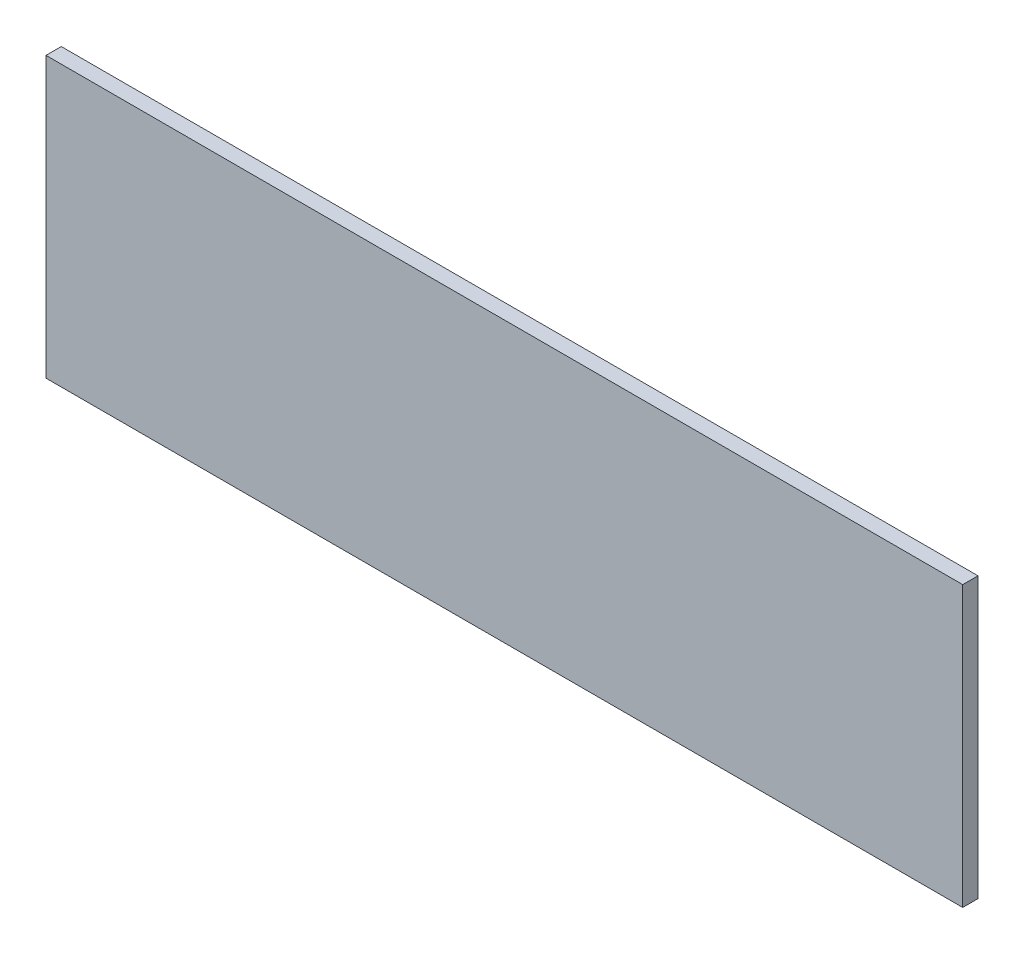
SolidWorks part; units mm, degrees
ref_plane "Plan de face" through (0, 0, 0) normal (0, 0, 1) x (1, 0, 0)
ref_plane "Plan de dessus" through (0, 0, 0) normal (0, 1, 0) x (1, 0, 0)
ref_plane "Plan de droite" through (0, 0, 0) normal (1, 0, 0) x (0, 0, -1)
sketch "Esquisse1" plane through (0, 0, 0) normal (0, 0, 1) x (1, 0, 0)
  line L1 (0, 0) -> (600, 0)
  line L2 (0, 0) -> (0, 183)
  line L3 (0, 183) -> (600, 183)
  line L4 (600, 0) -> (600, 183)
  dimension "D1" = 183
  dimension "D2" = 600
extrude "Boss.-Extru.1" add sketch "Esquisse1" along normal blind 10
